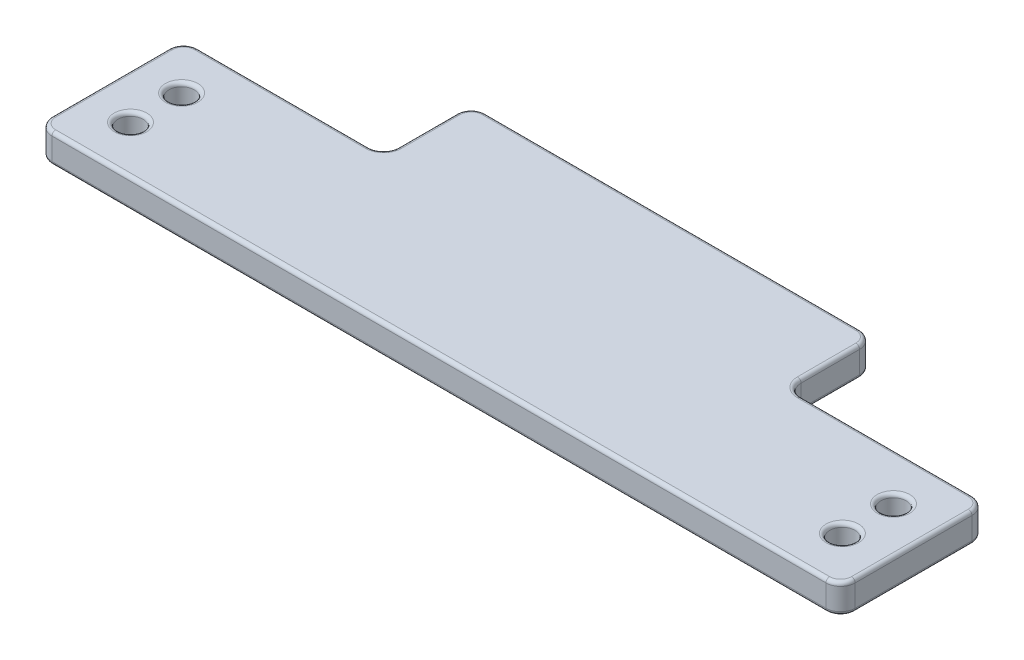
SolidWorks part; units mm, degrees
ref_plane "Front Plane" through (0, 0, 0) normal (0, 0, 1) x (1, 0, 0)
ref_plane "Top Plane" through (0, 0, 0) normal (0, 1, 0) x (1, 0, 0)
ref_plane "Right Plane" through (0, 0, 0) normal (1, 0, 0) x (0, 0, -1)
sketch "Sketch1" plane through (0, 0, 0) normal (0, 0, 1) x (1, 0, 0)
  line L0 (-37.5, 8.6498) -> (-37.5, -8.3502) construction
  line L1 (-42.5, -20.25) -> (42.5, -20.25)
  line L2 (-42.5, -20.25) -> (-42.5, 20.25)
  line L3 (-42.5, 20.25) -> (-32.6, 20.25)
  line L4 (42.5, -20.25) -> (42.5, 20.25)
  line L5 (-42.5, -20.25) -> (42.5, 20.25) construction
  line L6 (-42.5, 20.25) -> (42.5, -20.25) construction
  line L7 (0, 0) -> (0, 22.6037) construction
  line L8 (-32.6, 20.25) -> (-32.6, -14.75)
  line L9 (-32.6, -14.75) -> (32.6, -14.75)
  line L10 (32.6, -14.75) -> (32.6, 20.25)
  line L11 (32.6, 20.25) -> (42.5, 20.25)
  line L12 (0, 0) -> (-32.6, 0) construction
  line L13 (0, 0) -> (32.6, 0) construction
  line L14 (37.5, 8.6498) -> (37.5, -8.3502) construction
  circle A0 centre (-37.5, 8.6498) radius 1.325
  circle A1 centre (-37.5, -8.3502) radius 1.325
  circle A2 centre (37.5, -8.3502) radius 1.325
  circle A3 centre (37.5, 8.6498) radius 1.325
  point P0 (0, 0)
  dimension "D1" = 2.65
  dimension "D2" = 5.5
  dimension "D3" = 6.3998
  dimension "D4" = 17
  dimension "D5" = 35
  dimension "D6" = 4.9
  dimension "D7" = 5
  dimension "D8" = 75
extrude "Boss-Extrude1" add sketch "Sketch1" against normal mid plane 20
sketch "Sketch2" plane through (0, 0, 0) normal (1, 0, 0) x (0, 0, -1)
  line L0 (-10, -20.25) -> (-10, 20.25) construction
  line L1 (10, -20.25) -> (-10, -20.25)
  line L2 (10, -20.25) -> (10, -14.75)
  line L3 (10, -14.75) -> (-10, -14.75)
  line L4 (-10, -20.25) -> (-10, -14.75)
extrude "Boss-Extrude2" add sketch "Sketch2" against normal mid plane 110
sketch "Sketch4" plane through (0, -14.75, 0) normal (0, 1, 0) x (1, 0, 0)
  line L0 (0, 0) -> (-48.75, 0) construction
  line L1 (-48.75, -10) -> (-48.75, 10) construction
  line L2 (-55, -10) -> (-42.5, -10) construction
  line L3 (-55, 10) -> (-42.5, 10) construction
  point P10 (-48.75, 3.5)
  dimension "D1" = 3.5
hole_wizard "Tap Drill for #8-32 Tap1" positions "3DSketch1" profile "Sketch5" hole size "#8-32" standard "ANSI Inch" end condition through all
sketch3d "3DSketch1"
  point P0 (-48.75, -14.75, -3.5)
sketch "Sketch5" plane through (-48.75, -14.75, -3.5) normal (1, 0, 0) x (0, 0, 1)
  line L0 (0, 0) -> (0, 5.5)
  line L1 (0, 5.5) -> (1.7272, 5.5)
  line L2 (1.7272, 5.5) -> (1.7272, 0.635)
  line L3 (1.7272, 0.635) -> (2.3622, 0)
  line L5 (2.3622, 0) -> (0, 0)
  line L6 (-1.7272, 0.635) -> (-2.3622, 0) construction
  line L11 (0, -6.35) -> (0, 107.95) construction
  dimension "Thru Hole Dia." = 3.4544
  dimension "Thru Hole Depth" = 5.5
  dimension "Near C'Sink Dia." = 4.7244
  dimension "Near C'Sink Angle" = 90
mirror "Mirror1" about plane through (0, 0, 0) normal (0, 0, 1) of "Tap Drill for #8-32 Tap1"
mirror "Mirror2" about plane through (0, 0, 0) normal (1, 0, 0) of "Mirror1", "Tap Drill for #8-32 Tap1"
sketch "Sketch6" plane through (-32.6, 0, 0) normal (1, 0, 0) x (0, 0, -1)
  line L0 (10, -14.75) -> (10, 20.25) construction
  line L1 (-10, 20.25) -> (10, 20.25)
  line L2 (-10, 20.25) -> (-10, 15.4)
  line L3 (-10, 15.4) -> (10, 15.4)
  line L4 (10, 20.25) -> (10, 15.4)
  dimension "D1" = 4.85
extrude "Boss-Extrude3" add sketch "Sketch6" along normal blind 6.5
mirror "Mirror3" about plane through (0, 0, 0) normal (1, 0, 0) of "Boss-Extrude3"
sketch "Sketch7" plane through (0, 0, -10) normal (0, 0, -1) x (-1, 0, 0)
  line L0 (-32.6, -14.75) -> (32.6, -14.75) construction
  line L1 (-27.6, -14.75) -> (27.6, -14.75)
  line L2 (-27.6, -14.75) -> (-27.6, -20.25)
  line L3 (-27.6, -20.25) -> (27.6, -20.25)
  line L4 (27.6, -14.75) -> (27.6, -20.25)
  line L5 (55, -20.25) -> (-55, -20.25) construction
  line L6 (0, 0) -> (0, -14.75) construction
  line L7 (-32.6, 15.4) -> (-32.6, -14.75) construction
  dimension "D1" = 5
extrude "Boss-Extrude4" add sketch "Sketch7" along normal blind 12
ref_plane "Plane1" through (0, -20.35, 0) normal (0, -1, 0) x (-1, 0, 0)
sketch "Sketch9" plane through (0, -20.35, 0) normal (0, -1, 0) x (-1, 0, 0)
  line L8 (-55, -10) -> (55, -10)
  line L9 (55, -10) -> (55, 10)
  line L10 (55, 10) -> (27.6, 10)
  line L11 (27.6, 10) -> (27.6, 22)
  line L12 (27.6, 22) -> (-27.6, 22)
  line L13 (-27.6, 22) -> (-27.6, 10)
  line L14 (-27.6, 10) -> (-55, 10)
  line L15 (-55, 10) -> (-55, -10)
  line L16 (-55, -10) -> (55, -10)
  line L17 (55, -10) -> (55, 10)
  line L18 (55, 10) -> (27.6, 10)
  line L19 (27.6, 10) -> (27.6, 22)
  line L20 (27.6, 22) -> (-27.6, 22)
  line L21 (-27.6, 22) -> (-27.6, 10)
  line L22 (-27.6, 10) -> (-55, 10)
  line L23 (-55, 10) -> (-55, -10)
  circle A0 centre (-48.75, 3.5) radius 1.7272 construction
  circle A1 centre (-48.75, -3.5) radius 1.7272 construction
  circle A2 centre (48.75, -3.5) radius 1.7272 construction
  circle A3 centre (48.75, 3.5) radius 1.7272 construction
  circle A4 centre (-48.75, -3.5) radius 1.7272
  circle A5 centre (-48.75, 3.5) radius 1.7272
  circle A6 centre (48.75, -3.5) radius 1.7272
  circle A7 centre (48.75, 3.5) radius 1.7272
  dimension "D1" = 0
extrude "Boss-Extrude5" add sketch "Sketch9" along normal blind 4 separate body
fillet "Fillet4" radius 3 2 edges at (27.6, -17.5, -10) (-27.6, -17.5, -10)
fillet "Fillet1" radius 2 10 edges at (55, -14.75, 0) (-55, -14.75, 0) (42.5, 20.25, 0) (-42.5, 20.25, 0) (32.6, -14.75, 0) (42.5, -14.75, 0) (-32.6, -14.75, 0) (-42.5, -14.75, 0) (-32.6, 15.4, 0) (32.6, 15.4, 0)
fillet "Fillet5" radius 1.25 4 edges at (-26.1, 15.4, 0) (-26.1, 20.25, 0) (26.1, 15.4, 0) (26.1, 20.25, 0)
fillet "Fillet2" radius 1 5 edges at (-27.6, -20.25, -17.5) (0, -14.75, -22) (-28.4787, -20.25, -10.8787) (-55, -20.25, 0) (55, -20.25, 0)
fillet "Fillet6" radius 1 43 edges at (27.6, -20.25, -17.5) (0.5, -20.25, -22) (42.3, -20.25, -10) (28.4787, -20.25, -10.8787) (28.4787, -14.75, -10.8787) (-28.4787, -14.75, -10.8787) (-32.6, 0.325, -10) (32.6, 0.325, -10) (48.75, -14.75, -10) (33.925, 20.25, -10) (42.5, 2.75, -10) (41.9142, 19.6642, -10) (54.4142, -15.3358, -10) (-48.75, -14.75, -10) (-42.5, 2.75, -10) (-41.9142, 19.6642, -10) (-54.4142, -15.3358, -10) (-32.0142, -14.1642, -10) (-32.0142, 14.8142, -10) (32.0142, 14.8142, -10) (32.0142, -14.1642, -10) (43.0858, -14.1642, -10) (-43.0858, -14.1642, -10) (-26.1, 17.825, -10) (-33.925, 20.25, -10) (-28.975, 15.4, -10) (-26.4661, 19.8839, -10) (-26.4661, 15.7661, -10) (28.975, 15.4, -10) (26.1, 17.825, -10) (26.4661, 19.8839, -10) (26.4661, 15.7661, -10) (-27.6, -14.75, -17) (-27.6, -17.5, -22) (-27.6, -15.0429, -21.7071) (27.6, -18, -22) (-27.3071, -19.9571, -22) (27.6, -14.75, -17) (27.6, -15.0429, -21.7071) (-55, -18, -10) (55, -18, -10) (54.7071, -19.9571, -10) (-54.7071, -19.9571, -9.7071)
sketch "Sketch8" plane through (0, 0, 10) normal (0, 0, 1) x (1, 0, 0)
  line L5 (-27.35, 17.4) -> (27.35, 17.4)
  line L10 (34.6, -12.75) -> (34.6, 13.4)
  line L11 (30.6, 17.4) -> (27.35, 17.4)
  line L12 (-27.35, 17.4) -> (-30.6, 17.4)
  line L13 (-30.6, -16.75) -> (30.6, -16.75)
  line L14 (-34.6, 13.4) -> (-34.6, -12.75)
  line L15 (34.6, -12.75) -> (34.6, 13.4)
  line L16 (30.6, 17.4) -> (27.35, 17.4)
  line L17 (-27.35, 17.4) -> (-30.6, 17.4)
  line L18 (-30.6, -16.75) -> (30.6, -16.75)
  line L19 (-34.6, 13.4) -> (-34.6, -12.75)
  arc A8 (30.6, -16.75) -> (34.6, -12.75) centre (30.6, -12.75) ccw
  arc A9 (34.6, 13.4) -> (30.6, 17.4) centre (30.6, 13.4) ccw
  arc A10 (-30.6, 17.4) -> (-34.6, 13.4) centre (-30.6, 13.4) ccw
  arc A11 (-34.6, -12.75) -> (-30.6, -16.75) centre (-30.6, -12.75) ccw
  arc A12 (30.6, -16.75) -> (34.6, -12.75) centre (30.6, -12.75) ccw
  arc A13 (34.6, 13.4) -> (30.6, 17.4) centre (30.6, 13.4) ccw
  arc A14 (-30.6, 17.4) -> (-34.6, 13.4) centre (-30.6, 13.4) ccw
  arc A15 (-34.6, -12.75) -> (-30.6, -16.75) centre (-30.6, -12.75) ccw
  dimension "D1" = 2
split "Split1" trim tools "Sketch8" bodies to split 108 resulting bodies 109 110
fillet "Fillet7" radius 2 8 edges at (-55, -22.35, 10) (-55, -22.35, -10) (-27.6, -22.35, -10) (-27.6, -22.35, -22) (27.6, -22.35, -22) (27.6, -22.35, -10) (55, -22.35, 10) (55, -22.35, -10)
fillet "Fillet8" radius 0.5 40 edges at (54.4142, -24.35, 9.4142) (55, -24.35, 0) (54.4142, -24.35, -9.4142) (41.3, -24.35, -10) (28.1858, -24.35, -10.5858) (27.6, -24.35, -16) (27.0142, -24.35, -21.4142) (0, -24.35, -22) (-27.0142, -24.35, -21.4142) (-27.6, -24.35, -16) (-28.1858, -24.35, -10.5858) (-41.3, -24.35, -10) (-54.4142, -24.35, -9.4142) (-55, -24.35, 0) (-54.4142, -24.35, 9.4142) (54.4142, -20.35, 9.4142) (55, -20.35, 0) (54.4142, -20.35, -9.4142) (41.3, -20.35, -10) (28.1858, -20.35, -10.5858) (27.6, -20.35, -16) (27.0142, -20.35, -21.4142) (0, -20.35, -22) (-27.0142, -20.35, -21.4142) (-27.6, -20.35, -16) (-28.1858, -20.35, -10.5858) (-41.3, -20.35, -10) (-54.4142, -20.35, -9.4142) (-55, -20.35, 0) (-54.4142, -20.35, 9.4142) (0, -24.35, 10) (0, -20.35, 10) (48.75, -20.35, -5.2272) (48.75, -20.35, 1.7728) (48.75, -24.35, -5.2272) (48.75, -24.35, 1.7728) (-48.75, -24.35, -5.2272) (-48.75, -24.35, 1.7728) (-48.75, -20.35, 1.7728) (-48.75, -20.35, -5.2272)
delete or keep bodies "Body-Delete/Keep 1" type delete bodies bodies 110 109
